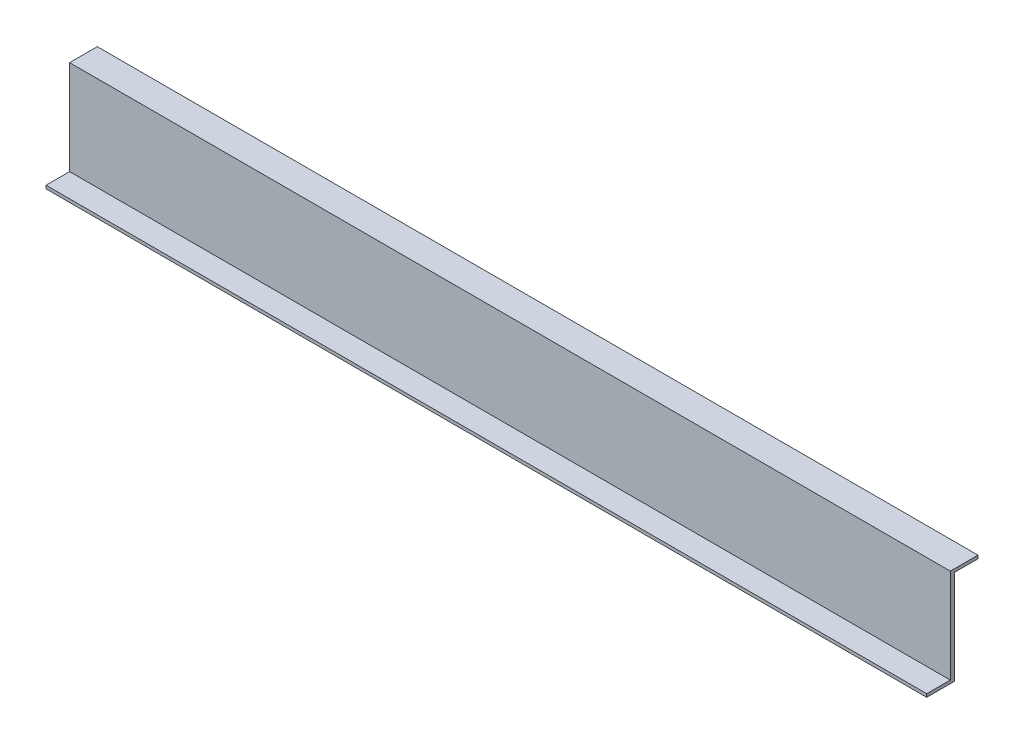
SolidWorks part; units mm, degrees
ref_plane "Front Plane" through (0, 0, 0) normal (0, 0, 1) x (1, 0, 0)
ref_plane "Top Plane" through (0, 0, 0) normal (0, 1, 0) x (1, 0, 0)
ref_plane "Right Plane" through (0, 0, 0) normal (1, 0, 0) x (0, 0, -1)
sketch "Sketch2" plane through (0, 0, 0) normal (0, 0, 1) x (1, 0, 0)
  line L1 (0, 0) -> (711.2, 0)
  line L2 (0, 0) -> (0, 78.74)
  line L3 (0, 78.74) -> (711.2, 78.74)
  line L4 (711.2, 0) -> (711.2, 78.74)
  dimension "D1" = 78.74
  dimension "D2" = 711.2
extrude "Boss-Extrude1" add sketch "Sketch2" along normal blind 711.2
sketch "Sketch4" plane through (711.2, 0, 0) normal (1, 0, 0) x (0, 0, -1)
  line L0 (-692.15, 2.54) -> (-692.15, 78.74)
  line L1 (-711.2, 78.74) -> (0, 78.74) construction
  line L2 (-692.15, 78.74) -> (-669.798, 78.74)
  line L3 (-669.798, 78.74) -> (-669.798, 76.2)
  line L4 (-669.798, 76.2) -> (-688.848, 76.2)
  line L5 (-688.848, 76.2) -> (-688.848, 0)
  line L6 (-711.2, 0) -> (0, 0) construction
  line L7 (-688.848, 0) -> (-711.2, 0)
  line L8 (-711.2, 0) -> (-711.2, 2.54)
  line L9 (-711.2, 0) -> (-711.2, 78.74) construction
  line L10 (-711.2, 2.54) -> (-692.15, 2.54)
  line L11 (-669.798, 78.74) -> (0, 78.74)
  line L12 (0, 78.74) -> (0, 0)
  line L13 (0, 0) -> (-688.848, 0)
  line L14 (-688.848, 76.2) -> (-669.798, 76.2)
  line L15 (-669.798, 78.74) -> (0, 78.74)
  line L16 (-711.2, 2.54) -> (-711.2, 78.74)
  line L17 (-711.2, 78.74) -> (-692.15, 78.74)
  line L18 (-692.15, 2.54) -> (-711.2, 2.54)
  line M3 (0, 0) -> (0, 78.74)
  line M4 (0, 78.74) -> (-711.2, 78.74)
  line M5 (-711.2, 78.74) -> (-711.2, 0)
  line M6 (-711.2, 0) -> (0, 0)
  dimension "D1" = 3.302
  dimension "D2" = 2.54
  dimension "D3" = 2.54
  dimension "D4" = 22.352
  dimension "D5" = 22.352
extrude "Cut-Extrude1" cut sketch "Sketch4" against normal through all contours L10 L0 M5 M4 | L4 L5 L3 M6 M3 M4 region at (711.2, 40.64, 701.675) region at (711.2, 39.336, 344.125)
